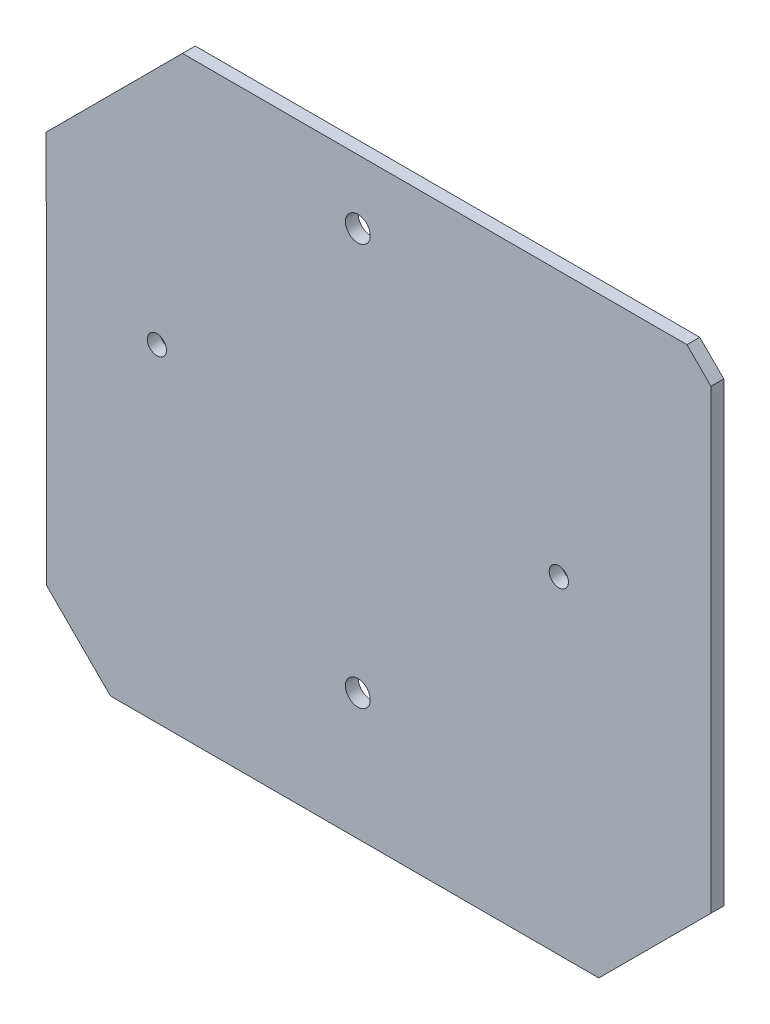
SolidWorks part; units mm, degrees
material "FR4_stuffedProtoboard"
ref_plane "Front Plane" through (0, 0, 0) normal (0, 0, 1) x (1, 0, 0)
ref_plane "Top Plane" through (0, 0, 0) normal (0, 1, 0) x (1, 0, 0)
ref_plane "Right Plane" through (0, 0, 0) normal (1, 0, 0) x (0, 0, -1)
sketch "Imported DXF" plane through (0, 0, 0) normal (0, 0, 1) x (1, 0, 0)
  line L0 (-21.6929, 33.1) -> (40.8929, 33.1)
  line L1 (41.2464, 32.9535) -> (43.9536, 30.2464)
  line L2 (44.1, 29.8929) -> (44.1, -26.6929)
  line L3 (43.9535, -27.0465) -> (30.2464, -40.7536)
  line L4 (29.8929, -40.9) -> (-30.6929, -40.9)
  line L5 (-31.0465, -40.7536) -> (-38.7536, -33.0464)
  line L6 (-38.9001, -32.6946) -> (-38.9148, 15.8797)
  line L7 (-38.7685, 16.2316) -> (-22.0464, 32.9536)
  line L8 (34.175, 6.26) -> (32.925, 6.26)
  line L9 (32.925, 6.26) -> (32.925, 8.26)
  line L10 (32.925, 8.26) -> (34.175, 8.26)
  line L11 (34.175, 8.26) -> (34.175, 6.26)
  line L12 (5.75, 8.485) -> (5.75, 9.735)
  line L13 (5.75, 9.735) -> (7.75, 9.735)
  line L14 (7.75, 9.735) -> (7.75, 8.485)
  line L15 (7.75, 8.485) -> (5.75, 8.485)
  line L16 (-4.91, -8.495) -> (-4.91, -9.745)
  line L17 (-4.91, -9.745) -> (-6.91, -9.745)
  line L18 (-6.91, -9.745) -> (-6.91, -8.495)
  line L19 (-6.91, -8.495) -> (-4.91, -8.495)
  line L20 (39.91, -3.075) -> (32.29, -3.075)
  line L21 (32.29, 3.275) -> (39.91, 3.275)
  line L22 (32.671, -3.075) -> (32.29, -3.075)
  line L23 (32.29, -3.075) -> (32.29, 3.275)
  line L24 (32.29, 3.275) -> (32.671, 3.275)
  line L25 (39.529, -3.075) -> (39.91, -3.075)
  line L26 (39.91, -3.075) -> (39.91, 3.275)
  line L27 (39.91, 3.275) -> (39.529, 3.275)
  line L28 (-3.81, 15.275) -> (3.81, 15.275)
  line L29 (3.81, 8.925) -> (-3.81, 8.925)
  line L30 (3.429, 15.275) -> (3.81, 15.275)
  line L31 (3.81, 15.275) -> (3.81, 8.925)
  line L32 (3.81, 8.925) -> (3.429, 8.925)
  line L33 (-3.429, 15.275) -> (-3.81, 15.275)
  line L34 (-3.81, 15.275) -> (-3.81, 8.925)
  line L35 (-3.81, 8.925) -> (-3.429, 8.925)
  line L36 (3.81, -15.275) -> (-3.81, -15.275)
  line L37 (-3.81, -8.925) -> (3.81, -8.925)
  line L38 (-3.429, -15.275) -> (-3.81, -15.275)
  line L39 (-3.81, -15.275) -> (-3.81, -8.925)
  line L40 (-3.81, -8.925) -> (-3.429, -8.925)
  line L41 (3.429, -15.275) -> (3.81, -15.275)
  line L42 (3.81, -15.275) -> (3.81, -8.925)
  line L43 (3.81, -8.925) -> (3.429, -8.925)
  line L44 (0, 37.7984) -> (0, -46.2816) construction
  line L45 (-65.7891, 0) -> (80.4964, 0) construction
  arc A0 (41.2464, 32.9535) -> (40.8929, 33.1) centre (40.8929, 32.6) ccw
  arc A1 (44.1, 29.8929) -> (43.9535, 30.2464) centre (43.6, 29.8929) ccw
  arc A2 (43.9535, -27.0465) -> (44.1, -26.6929) centre (43.6, -26.6929) ccw
  arc A3 (29.8929, -40.9) -> (30.2464, -40.7536) centre (29.8929, -40.4) ccw
  arc A4 (-31.0465, -40.7536) -> (-30.6929, -40.9) centre (-30.6929, -40.4) ccw
  arc A5 (-38.9001, -32.6946) -> (-38.7537, -33.0464) centre (-38.4001, -32.6928) ccw
  arc A6 (-38.7685, 16.2316) -> (-38.9149, 15.8796) centre (-38.4155, 15.8783) ccw
  arc A7 (-21.6929, 33.1) -> (-22.0465, 32.9535) centre (-21.6929, 32.6) ccw
  circle A8 centre (-25.1, 0) radius 1.2
  circle A9 centre (25.1, 0) radius 1.2
  circle A10 centre (0, 25.1) radius 1.55
  circle A11 centre (0, -25.1) radius 1.55
  circle A12 centre (40.481, 2.989) radius 0.254
  circle A13 centre (-4.381, 9.211) radius 0.254
  circle A14 centre (4.381, -9.211) radius 0.254
  point P20 (0, 0)
  point P40 (33.55, 7.26)
  point P45 (6.75, 9.11)
  point P50 (-5.91, -9.12)
  point P55 (38.1, 26.1)
  point P56 (23.4, 23.4)
  point P57 (-23.4, 23.4)
  point P58 (-23.4, -23.4)
  point P59 (23.4, -23.4)
  point P60 (36.1, 0.1)
  point P71 (0, 12.1)
  point P82 (0, -12.1)
  dimension "D1" = 3.1
sketch "Outline" plane through (0, 0, 0) normal (0, 0, 1) x (1, 0, 0)
  line L0 (-21.9, 33.1) -> (41.1, 33.1)
  line L2 (44.1, -26.9) -> (30.1, -40.9)
  line L3 (30.1, -40.9) -> (-30.9, -40.9)
  line L4 (-30.9, -40.9) -> (-38.9, -32.9)
  line L5 (-38.9, -32.9) -> (-38.9149, 16.0852)
  line L6 (-38.9149, 16.0852) -> (-21.9, 33.1)
  line L7 (-38.7685, 16.2316) -> (-22.0464, 32.9536) construction
  line L8 (-21.6929, 33.1) -> (40.8929, 33.1) construction
  line L13 (-38.9001, -32.6946) -> (-38.9148, 15.8797) construction
  line L14 (-31.0465, -40.7536) -> (-38.7536, -33.0464) construction
  line L15 (29.8929, -40.9) -> (-30.6929, -40.9) construction
  line L16 (43.9535, -27.0465) -> (30.2464, -40.7536) construction
  line L18 (41.1, 33.1) -> (44.1, 30.1)
  line L19 (44.1, 30.1) -> (44.1, -26.9)
  line L20 (44.1, 29.8929) -> (44.1, -26.6929) construction
  line L21 (41.2464, 32.9535) -> (43.9536, 30.2464) construction
extrude "Boss-Extrude1" add sketch "Outline" along normal blind 1.6
sketch "Connector locations" plane through (0, 0, 1.6) normal (0, 0, 1) x (1, 0, 0)
  line L1 (24.5314, 22.2686) -> (22.2686, 24.5314)
  line L2 (38.1, 27.7) -> (38.1, 24.5)
  line L3 (22.2686, -24.5314) -> (24.5314, -22.2686)
  line L4 (0, 0) -> (23.4, 23.4) construction
  line L5 (-24.5314, -22.2686) -> (-22.2686, -24.5314)
  line L6 (-22.2686, 24.5314) -> (-24.5314, 22.2686)
  line L9 (-21.6929, 33.1) -> (40.8929, 33.1) construction
  line L10 (-65.7891, 0) -> (80.4964, 0) construction
  point P13 (38.1, 26.1)
  dimension "D1" = 45
  dimension "D3" = 45
  dimension "D4" = 33.0926
  dimension "D6" = 3.2
sketch "Sketch3" plane through (0, 0, 1.6) normal (0, 0, 1) x (1, 0, 0)
  circle A0 centre (0, 25.1) radius 1.55
  circle A1 centre (25.1, 0) radius 1.2
  circle A2 centre (0, -25.1) radius 1.55
  circle A3 centre (-25.1, 0) radius 1.2
  circle A4 centre (25.1, 0) radius 1.2 construction
  circle A5 centre (0, 25.1) radius 1.55 construction
  circle A6 centre (-25.1, 0) radius 1.2 construction
  circle A7 centre (0, -25.1) radius 1.55 construction
extrude "Cut-Extrude3" cut sketch "Sketch3" against normal up to next
sketch "Press Fit Nut Locations" plane through (0, 0, 1.6) normal (0, 0, 1) x (1, 0, 0)
  circle A0 centre (-27.0307, 27.0307) radius 2.78 construction
  circle A1 centre (27.0307, 27.0307) radius 2.78 construction
  circle A2 centre (-27.0307, -27.0307) radius 2.78 construction
  circle A3 centre (27.0307, -27.0307) radius 2.78 construction
  circle A4 centre (-27.0307, 27.0307) radius 2.78
  circle A5 centre (27.0307, 27.0307) radius 2.78
  circle A6 centre (-27.0307, -27.0307) radius 2.78
  circle A7 centre (27.0307, -27.0307) radius 2.78
sketch "Frame Boss Lines" plane through (0, 0, 1.6) normal (0, 0, 1) x (1, 0, 0)
  line L0 (-41.5, 37.8828) -> (-41.5, -46.4929)
  line L1 (-41.5, -37) -> (-41.5, -41.5) construction
  line L2 (41.5, -37) -> (41.5, -41.5) construction
  line L3 (-41.5, -37) -> (-41.5, -41.5) construction
  line L4 (41.5, -37) -> (41.5, -41.5) construction
  line L7 (41.5, 37.8828) -> (41.5, -46.4929)
  point P6 (0, 0)
  point P7 (0, 0)
  point P9 (0, 0)
  point P10 (41.5, -42.4737)
  point P11 (0, 0)
  point P14 (0, 0)
  point P15 (-41.5, -43.0614)
  point P16 (-41.5, -46.4929)
